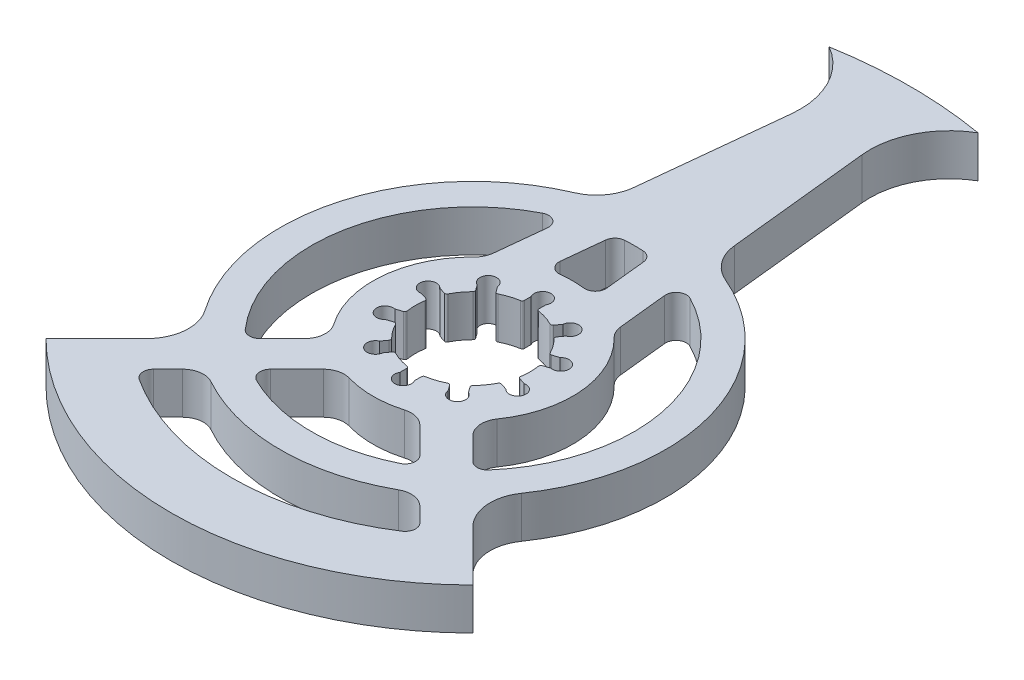
SolidWorks part; units mm, degrees
material "AISI Type A2 Tool Steel"
ref_plane "Front Plane" through (0, 0, 0) normal (0, 0, 1) x (1, 0, 0)
ref_plane "Top Plane" through (0, 0, 0) normal (0, 1, 0) x (1, 0, 0)
ref_plane "Right Plane" through (0, 0, 0) normal (1, 0, 0) x (0, 0, -1)
other "Center of Mass"
other "Bounding Box"
ref_plane "Default Plane" through (0, 2.286, 19.05) normal (0, -1, 0) x (-1, 0, 0)
sketch "Sketch1" plane through (0, 0, 0) normal (0, 1, 0) x (1, 0, 0)
  circle A0 centre (0, 0) radius 133.35 construction
  circle A1 centre (0, 0) radius 30.48
  circle A2 centre (0, 0) radius 17.4625
  dimension "D1" = 266.7
  dimension "D2" = 60.96
  dimension "D3" = 34.925
extrude "Boss-Extrude1" add sketch "Sketch1" along normal mid plane 12.7
sketch "Sketch2" plane through (0, 6.35, 0) normal (0, 1, 0) x (1, 0, 0)
  line L0 (-10.795, 107.95) -> (-19.6961, 23.2614)
  line L1 (19.6961, 23.2614) -> (10.795, 107.95)
  line L4 (0, 0) -> (0, 133.35) construction
  line L5 (-10.795, 107.95) -> (0, 107.95) construction
  line L6 (0, 107.95) -> (10.795, 107.95) construction
  line L7 (-22.6939, 131.4048) -> (0, 0) construction
  line L8 (-22.6939, 131.4048) -> (125.4677, 45.1673) construction
  circle A0 centre (0, 0) radius 133.35 construction
  circle A1 centre (0, 0) radius 133.35 construction
  arc A2 (-22.6939, 131.4048) -> (22.6939, 131.4048) centre (0, 0) cw
  arc A3 (-22.6939, 131.4048) -> (-10.795, 107.95) centre (-34.8727, 110.4807) cw
  circle A5 centre (0, 0) radius 30.48
  arc A6 (19.6961, 23.2614) -> (-19.6961, 23.2614) centre (0, 0) ccw
  arc A7 (-19.6961, 23.2614) -> (19.6961, 23.2614) centre (0, 0) ccw construction
  arc A8 (10.795, 107.95) -> (22.6939, 131.4048) centre (34.8727, 110.4807) cw
  dimension "D4" = 25.4
  dimension "D5" = 6
  dimension "D6" = 10.795
  dimension "D1" = 50
  dimension "D2" = 0
extrude "Boss-Extrude2" add sketch "Sketch2" against normal through all
sketch "Sketch3" plane through (0, 6.35, 0) normal (0, 1, 0) x (1, 0, 0)
  line L0 (-65.1069, -65.1069) -> (-21.5526, -21.5526)
  line L1 (21.5526, -21.5526) -> (65.1069, -65.1069)
  line L2 (0, -30.48) -> (0, -92.075) construction
  line L4 (-21.5526, -21.5526) -> (0, 0) construction
  line L5 (0, 0) -> (21.5526, -21.5526) construction
  arc A0 (-65.1069, -65.1069) -> (65.1069, -65.1069) centre (0, 0) ccw
  circle A1 centre (0, 0) radius 30.48 construction
  arc A3 (-21.5526, -21.5526) -> (21.5526, -21.5526) centre (0, 0) ccw
  point P13 (0, -92.075)
  dimension "D2" = 92.075
  dimension "D1" = 90
extrude "Boss-Extrude3" add sketch "Sketch3" against normal through all
sketch "Sketch5" plane through (0, 6.35, 0) normal (0, 1, 0) x (1, 0, 0)
  line L0 (0, 17.4625) -> (0, 21.2725) construction
  line L2 (-2.2225, 17.3205) -> (2.2225, 17.3205)
  line L3 (-2.2225, 17.3205) -> (-2.2225, 20.0168)
  line L5 (2.2225, 17.3205) -> (2.2225, 20.0168)
  arc A0 (2.2225, 20.0168) -> (-2.2225, 20.0168) centre (0, 21.2725) ccw
  circle A1 centre (0, 0) radius 17.4625 construction
  circle A2 centre (0, 21.2725) radius 4.5847 construction
  dimension "D2" = 5.1054
  dimension "D4" = 9.1694
  dimension "D1" = 3.81
  dimension "D3" = 4.445
extrude "Cut-Extrude2" cut sketch "Sketch5" against normal through all
pattern_circular "CirPattern1" count 10 over 360 about axis through (0, 6.35, 0) along (0, -1, 0) of "Cut-Extrude2"
sketch "Sketch6" plane through (0, 6.35, 0) normal (0, 1, 0) x (1, 0, 0)
  circle A0 centre (0, 0) radius 17.526
  arc A1 (-11.9788, 12.7062) -> (-15.786, 7.466) centre (0, 0) ccw construction
  dimension "D1" = 0.0635
extrude "Cut-Extrude3" cut sketch "Sketch6" against normal through all
sketch "Sketch7" plane through (0, 6.35, 0) normal (0, 1, 0) x (1, 0, 0)
  line L0 (-43.3087, -59.4732) -> (-11.8976, -28.062)
  line L1 (11.8976, -28.062) -> (43.3087, -59.4732)
  line L3 (-21.5526, -21.5526) -> (-65.1069, -65.1069) construction
  line L4 (65.1069, -65.1069) -> (21.5526, -21.5526) construction
  line L5 (-43.3087, -59.4732) -> (-51.391, -51.391) construction
  line L6 (43.3087, -59.4732) -> (51.391, -51.391) construction
  arc A0 (-11.8976, -28.062) -> (11.8976, -28.062) centre (0, 0) ccw
  arc A1 (-43.3087, -59.4732) -> (43.3087, -59.4732) centre (0, 0) ccw
  arc A2 (-65.1069, -65.1069) -> (65.1069, -65.1069) centre (0, 0) ccw construction
  arc A4 (21.5526, -21.5526) -> (19.6961, 23.2614) centre (0, 0) ccw construction
  dimension "D1" = 18.5039
  dimension "D2" = 11.43
extrude "Cut-Extrude4" cut sketch "Sketch7" against normal through all
sketch "Sketch8" plane through (0, 6.35, 0) normal (0, 1, 0) x (1, 0, 0)
  circle A0 centre (0, 0) radius 49.2125
  circle A1 centre (0, 0) radius 58.7375
  dimension "D1" = 9.525
  dimension "D2" = 117.475
extrude "Boss-Extrude4" add sketch "Sketch8" against normal through all
sketch "Sketch11" plane through (0, 6.35, 0) normal (0, 1, 0) x (1, 0, 0)
  line L0 (-7.5441, 29.5316) -> (-5.5081, 48.9033)
  line L1 (5.5081, 48.9033) -> (7.5441, 29.5316)
  line L3 (-17.2986, 46.072) -> (-19.6961, 23.2614) construction
  line L4 (19.6961, 23.2614) -> (17.2986, 46.072) construction
  line L5 (-6.5261, 39.2174) -> (-17.8935, 40.4122) construction
  line L6 (6.5261, 39.2174) -> (17.8935, 40.4122) construction
  arc A0 (-7.5441, 29.5316) -> (7.5441, 29.5316) centre (0, 0) cw
  arc A1 (-5.5081, 48.9033) -> (5.5081, 48.9033) centre (0, 0) cw
  arc A2 (-19.6961, 23.2614) -> (-21.5526, -21.5526) centre (0, 0) ccw construction
  arc A3 (-17.2986, 46.072) -> (-34.7985, -34.7985) centre (0, 0) ccw construction
  dimension "D1" = 11.43
extrude "Cut-Extrude6" cut sketch "Sketch11" against normal through all
fillet "Fillet1" radius 6.35 8 edges at (-21.5526, 0, 21.5526) (21.5526, 0, 21.5526) (19.6961, 0, -23.2614) (-19.6961, 0, -23.2614) (11.8976, 0, 28.062) (-11.8976, 0, 28.062) (32.6575, 0, 48.8219) (-32.6575, 0, 48.8219)
fillet "Fillet6" radius 0.635 20 edges at (-12.0164, 0, -12.758) (-15.8469, 0, -7.4858) (-17.2204, 0, -3.2584) (-17.2204, 0, 3.2584) (-15.8469, 0, 7.4858) (-12.0164, 0, 12.758) (-8.4203, 0, 15.3707) (-2.2225, 0, 17.3845) (2.2225, 0, 17.3845) (8.4203, 0, 15.3707) (12.0164, 0, 12.758) (15.8469, 0, 7.4858) (17.2204, 0, 3.2584) (17.2204, 0, -3.2584) (15.8469, 0, -7.4858) (12.0164, 0, -12.758) (8.4203, 0, -15.3707) (2.2225, 0, -17.3845) (-2.2225, 0, -17.3845) (-8.4203, 0, -15.3707)
fillet "Fillet7" radius 3.175 12 edges at (-25.7647, 0, 41.9291) (25.7647, 0, 41.9291) (34.7985, 0, 34.7985) (-34.7985, 0, 34.7985) (-17.2986, 0, -46.072) (17.2986, 0, -46.072) (43.3087, 0, 59.4732) (-43.3087, 0, 59.4732) (-7.5441, 0, -29.5316) (7.5441, 0, -29.5316) (5.5081, 0, -48.9033) (-5.5081, 0, -48.9033)
fillet "Fillet8" radius 12.7 4 edges at (-16.2071, 0, -56.4573) (16.2071, 0, -56.4573) (41.5337, 0, 41.5337) (-41.5337, 0, 41.5337)
equation "\"Unit Measure\"= \"BoundingVolume\" / \"Thickness\"'in^2"
